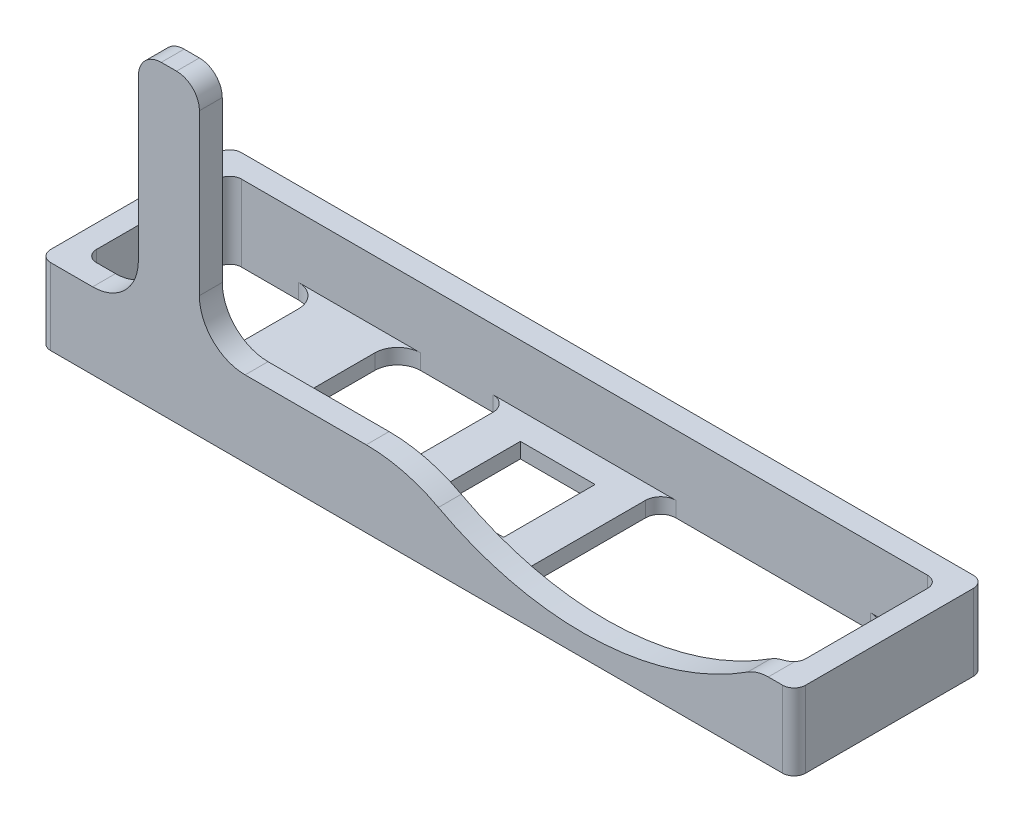
SolidWorks part; units mm, degrees
ref_plane "Front Plane" through (0, 0, 0) normal (0, 0, 1) x (1, 0, 0)
ref_plane "Top Plane" through (0, 0, 0) normal (0, 1, 0) x (1, 0, 0)
ref_plane "Right Plane" through (0, 0, 0) normal (1, 0, 0) x (0, 0, -1)
sketch "Sketch1" plane through (0, 0, 0) normal (0, 1, 0) x (1, 0, 0)
  line L0 (-49.5, -12.5) -> (-49.5, 12.5)
  line L1 (-46.5, -9.5) -> (46.5, -9.5)
  line L2 (-46.5, -9.5) -> (-46.5, 9.5)
  line L3 (-46.5, 9.5) -> (46.5, 9.5)
  line L4 (46.5, -9.5) -> (46.5, 9.5)
  line L5 (-46.5, -9.5) -> (46.5, 9.5) construction
  line L6 (-46.5, 9.5) -> (46.5, -9.5) construction
  line L7 (-49.5, 12.5) -> (49.5, 12.5)
  line L8 (49.5, -12.5) -> (49.5, 12.5)
  line L9 (-49.5, -12.5) -> (49.5, -12.5)
  point P0 (0, 0)
  dimension "D1" = 19
  dimension "D2" = 93
  dimension "D3" = 3
extrude "Boss-Extrude1" add sketch "Sketch1" along normal blind 10
sketch "Sketch2" plane through (0, 0, 12.5) normal (0, 0, 1) x (1, 0, 0)
  circle A0 centre (21.7809, 42.8531) radius 40
  dimension "D1" = 80
extrude "Cut-Extrude1" cut sketch "Sketch2" against normal blind 8
sketch "Sketch5" plane through (0, 0, 0) normal (0, -1, 0) x (1, 0, 0)
  line L7 (49.5, -12.5) -> (-49.5, -12.5) construction
  line L8 (-24.5, -12.5) -> (-34.5, -12.5)
  line L9 (-24.5, -12.5) -> (-24.5, 12.5)
  line L10 (-24.5, 12.5) -> (-34.5, 12.5)
  line L11 (-34.5, -12.5) -> (-34.5, 12.5)
  line L12 (-49.5, 12.5) -> (49.5, 12.5) construction
  line L13 (-49.5, -12.5) -> (-49.5, 12.5) construction
  dimension "D1" = 10
  dimension "D2" = 15
extrude "Boss-Extrude5" add sketch "Sketch5" against normal blind 2
sketch "Sketch6" plane through (0, 0, 0) normal (0, -1, 0) x (1, 0, 0)
  line L0 (46.5, -9.5) -> (-24.5, -9.5) construction
  line L1 (46.5, 9.5) -> (40.5, 9.5)
  line L2 (46.5, 9.5) -> (46.5, -9.5)
  line L3 (46.5, -9.5) -> (40.5, -9.5)
  line L4 (40.5, 9.5) -> (40.5, -9.5)
  dimension "D1" = 6
extrude "Boss-Extrude6" add sketch "Sketch6" against normal blind 2
sketch "Sketch7" plane through (0, 10, 0) normal (0, 1, 0) x (1, 0, 0)
  line L0 (-49.5, -12.5) -> (-1.0373, -12.5) construction
  line L1 (-36.5, -12.5) -> (-28.5, -12.5)
  line L2 (-36.5, -12.5) -> (-36.5, -9.5)
  line L3 (-36.5, -9.5) -> (-28.5, -9.5)
  line L4 (-28.5, -12.5) -> (-28.5, -9.5)
  line L5 (-46.5, -9.5) -> (-1.0373, -9.5) construction
  line L6 (-49.5, 12.5) -> (-49.5, -12.5) construction
  dimension "D1" = 8
  dimension "D2" = 13
extrude "Boss-Extrude7" add sketch "Sketch7" along normal blind 30
fillet "Fillet5" radius 3 6 edges at (-34.5, 1, 9.5) (-34.5, 1, -9.5) (-24.5, 1, 9.5) (-24.5, 1, -9.5) (40.5, 1, 9.5) (40.5, 1, -9.5)
fillet "Fillet7" radius 5 1 edges at (44.5992, 10, 11)
fillet "Fillet8" radius 20 1 edges at (-1.0373, 10, 11)
fillet "Fillet9" radius 1.5 8 edges at (-46.5, 5, 9.5) (-46.5, 5, -9.5) (46.5, 6, -9.5) (46.5, 6, 9.5) (49.5, 5, 12.5) (49.5, 5, -12.5) (-49.5, 5, 12.5) (-49.5, 5, -12.5)
fillet "Fillet10" radius 6 2 edges at (-36.5, 10, 11) (-28.5, 10, 11)
fillet "Fillet11" radius 3 2 edges at (-28.5, 40, 11) (-36.5, 40, 11)
sketch "Sketch8" plane through (0, 0, 0) normal (0, -1, 0) x (1, 0, 0)
  line L0 (48, -12.5) -> (-48, -12.5) construction
  line L1 (-10, 12.5) -> (10, 12.5)
  line L2 (-10, 12.5) -> (-10, -12.5)
  line L3 (-10, -12.5) -> (10, -12.5)
  line L4 (10, 12.5) -> (10, -12.5)
  line L5 (-10, 12.5) -> (10, -12.5) construction
  line L6 (-10, -12.5) -> (10, 12.5) construction
  point P0 (0, 0)
  dimension "D1" = 20
extrude "Boss-Extrude8" add sketch "Sketch8" against normal up to surface (2 mm away) up to face at (-29.5, 2, 0)
sketch "Sketch9" plane through (0, 0, 0) normal (0, -1, 0) x (1, 0, 0)
  line L1 (-4.9, 6) -> (4.9, 6)
  line L2 (-4.9, 6) -> (-4.9, -6)
  line L3 (-4.9, -6) -> (4.9, -6)
  line L4 (4.9, 6) -> (4.9, -6)
  line L5 (-4.9, 6) -> (4.9, -6) construction
  line L6 (-4.9, -6) -> (4.9, 6) construction
  point P0 (0, 0)
  dimension "D1" = 9.8
  dimension "D2" = 12
extrude "Boss-Extrude9" add sketch "Sketch9" along normal blind 10
sketch "Sketch10" plane through (4.9, 0, 0) normal (1, 0, 0) x (0, 0, -1)
  circle A0 centre (0, -5) radius 2
  dimension "D1" = 4
  dimension "D2" = 5
extrude "Cut-Extrude2" cut sketch "Sketch10" against normal blind 23
fillet "Fillet12" radius 6 2 edges at (0, -10, 6) (0, -10, -6)
sketch "Sketch12" plane through (0, 0, 0) normal (0, -1, 0) x (1, 0, 0)
  line L0 (-4.9, 6) -> (4.9, 6)
  line L1 (4.9, 6) -> (4.9, -6)
  line L2 (4.9, -6) -> (-4.9, -6)
  line L3 (-4.9, -6) -> (-4.9, 6)
extrude "Cut-Extrude5" cut sketch "Sketch12" against normal through all both and the other way through all
fillet "Fillet13" radius 2 4 edges at (10, 1, -9.5) (-10, 1, -9.5) (-10, 1, 9.5) (10, 1, 9.5)
